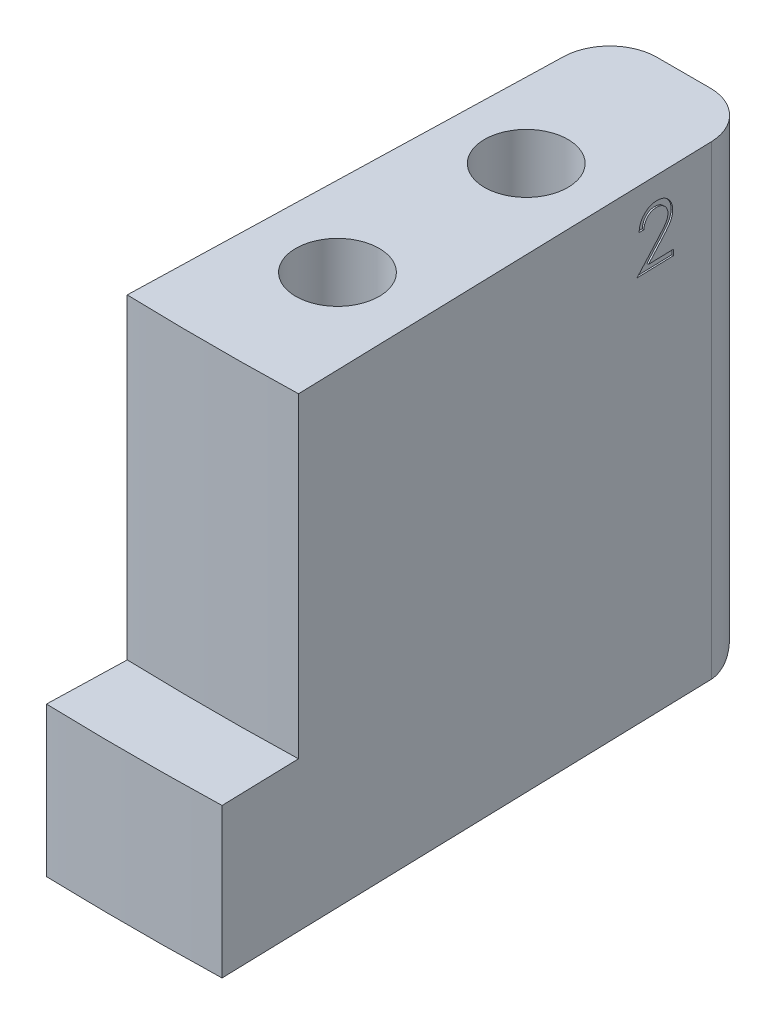
SolidWorks part; units mm, degrees
ref_plane "前视基准面" through (0, 0, 0) normal (0, 0, 1) x (1, 0, 0)
ref_plane "上视基准面" through (0, 0, 0) normal (0, 1, 0) x (1, 0, 0)
ref_plane "右视基准面" through (0, 0, 0) normal (1, 0, 0) x (0, 0, -1)
ref_axis "顶盖中心轴" through (0, -55, 0) along (0, 1, 0)
sketch "草图1" plane through (0, 0, 0) normal (0, 1, 0) x (1, 0, 0)
  line L0 (-4.7487, -170.0072) -> (-4.8586, -173.9402) construction
  line L1 (0, 0) -> (0, -125.794) construction
  line L3 (-4.6089, -165) -> (4.6089, -165)
  line L4 (-4.6089, -165) -> (-5.5843, -199.922)
  line L5 (4.6089, -165) -> (5.5843, -199.922)
  arc A0 (-5.4447, -194.924) -> (5.4447, -194.924) centre (0, 0) ccw
  arc A1 (-5.5843, -199.922) -> (5.5843, -199.922) centre (0, 0) ccw
  dimension "D1" = 1.6
  dimension "D2" = 195
  dimension "D4" = 200
  dimension "D3" = 165
extrude "主体" add sketch "草图1" along normal blind 29.6 contours L4 A0 L5 L3 region at (0, 0, 180.4033)
extrude "插销" add sketch "草图1<3>" along normal blind 9.5 contours L4 A1 L5 A0 region at (0, 0, 197.4849)
sketch "草图1<3>" plane through (0, 0, 0) normal (0, 1, 0) x (1, 0, 0) same geometry as "草图1"
ref_plane "对称面" through (0, 0, 0) normal (1, 0, 0) x (0, 0, -1)
fillet "圆角1" radius 3 3 edges at (-4.6089, 14.8, 165) (4.6089, 14.8, 165) (0, 0, 165)
hole_wizard "M5 间隙孔1" positions "草图4" profile "草图5" hole size "M5" standard "ISO" end condition up to next
sketch "草图4" plane through (0, 29.6, 0) normal (0, 1, 0) x (1, 0, 0)
  line L0 (0, -13.75) -> (0, 13.75) construction
  point P0 (0, -187)
  point P2 (0, -175)
  dimension "D1" = 175
  dimension "D2" = 187
sketch "草图5" plane through (0, 29.6, 187) normal (1, 0, 0) x (0, 0, 1)
  line L0 (0, 0) -> (0, 29.6)
  line L1 (0, 29.6) -> (2.65, 29.6)
  line L2 (2.65, 29.6) -> (2.65, 0)
  line L5 (2.65, 0) -> (0, 0)
  line L11 (0, -6.35) -> (0, 107.95) construction
  dimension "通孔孔直径" = 5.3
  dimension "通孔孔深度" = 29.6
sketch "草图6" plane through (0, 0, 0) normal (0, -1, 0) x (1, 0, 0)
  line L1 (0, 179.792) -> (-4.15, 177.396)
  line L2 (-4.15, 177.396) -> (-4.15, 172.604)
  line L3 (-4.15, 172.604) -> (0, 170.208)
  line L4 (0, 170.208) -> (4.15, 172.604)
  line L5 (4.15, 172.604) -> (4.15, 177.396)
  line L6 (4.15, 177.396) -> (0, 179.792)
  line L7 (0, 191.792) -> (-4.15, 189.396)
  line L8 (-4.15, 189.396) -> (-4.15, 184.604)
  line L9 (-4.15, 184.604) -> (0, 182.208)
  line L10 (0, 182.208) -> (4.15, 184.604)
  line L11 (4.15, 184.604) -> (4.15, 189.396)
  line L12 (4.15, 189.396) -> (0, 191.792)
  circle A0 centre (0, 175) radius 4.15 construction
  circle A1 centre (0, 187) radius 4.15 construction
  point P9 (0, 182.208)
  point P17 (0, 170.208)
  dimension "D1" = 8.3
  dimension "D2" = 8.3
extrude "切除-拉伸1" cut sketch "草图6" against normal blind 5
sketch "草图7" plane through (0, 0, 0) normal (0.9996, 0, -0.0279) x (-0.0279, 0, -0.9996)
  line L0 (-167.9817, 0.0012) -> (-167.9817, 29.6) construction
  line L2 (-167.9817, 29.6) -> (-195, 29.6) construction
  text T0 "2"
  point P1 (0, 0)
  point P4 (0, 0)
  point P6 (-170.6934, 29.6)
  dimension "D1" = 5
  dimension "D2" = 5
extrude "切除-拉伸2" cut sketch "草图7" against normal blind 0.1
